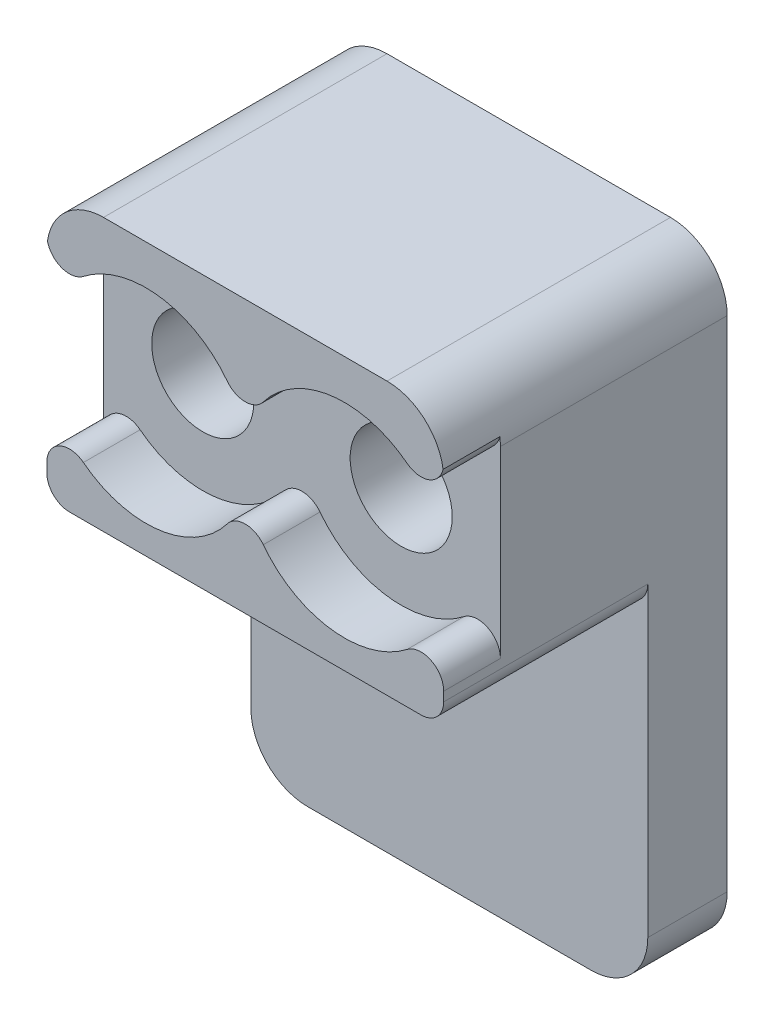
SolidWorks part; units mm, degrees
other "Markup1"
sketch "Sketch4" plane through (17.78, 27.432, 12.7) normal (0.9333, 0.0177, 0.3587) x (0.3579, 0.0365, -0.933)
ref_plane "Front Plane" through (0, 0, 0) normal (0, 0, 1) x (1, 0, 0)
ref_plane "Top Plane" through (0, 0, 0) normal (0, 1, 0) x (1, 0, 0)
ref_plane "Right Plane" through (0, 0, 0) normal (1, 0, 0) x (0, 0, -1)
sketch "Sketch1" plane through (0, 0, 0) normal (1, 0, 0) x (0, 0, -1)
  line L0 (0, 0) -> (0, 27.432)
  line L1 (0, 27.432) -> (-12.7, 27.432)
  line L2 (-12.7, 27.432) -> (-12.7, 15.24)
  line L3 (-12.7, 15.24) -> (-3.556, 15.24)
  line L4 (-3.556, 15.24) -> (-3.556, 0)
  line L5 (-3.556, 0) -> (0, 0)
  point P3 (-1.778, 0)
  dimension "D1" = 3.556
  dimension "D2" = 15.24
  dimension "D3" = 12.192
  dimension "D4" = 12.7
extrude "Boss-Extrude1" add sketch "Sketch1" along normal blind 17.78 contours L5 L0 L1 L2 L3 L4
sketch "Sketch2" plane through (0, 0, 12.7) normal (0, 0, 1) x (1, 0, 0)
  line L0 (8.89, 27.432) -> (8.89, 15.24) construction
  line L1 (17.78, 27.432) -> (0, 27.432) construction
  line L2 (17.78, 15.24) -> (0, 15.24) construction
  circle A0 centre (4.445, 21.082) radius 2.286
  circle A1 centre (13.335, 21.082) radius 2.286
  dimension "D2" = 4.572
  dimension "D1" = 4.445
  dimension "D3" = 6.35
extrude "Cut-Extrude1" cut sketch "Sketch2" against normal through all
sketch "Sketch3" plane through (0, 0, 12.7) normal (0, 0, 1) x (1, 0, 0)
  circle A0 centre (4.445, 21.082) radius 4.572
  circle A1 centre (13.335, 21.082) radius 4.572
  circle M2 centre (4.445, 21.082) radius 2.286
  circle M3 centre (13.335, 21.082) radius 2.286
  line M4 (0, 27.432) -> (0, 15.24)
  line M6 (17.78, 15.24) -> (17.78, 27.432)
  dimension "D1" = 9.144
extrude "Cut-Extrude2" cut sketch "Sketch3" against normal blind 2.54 contours A1 A0 M4 M2 | A1 A0 M6 M3 | A0 A1
fillet "Fillet1" radius 1.016 8 edges at (0, 20.0119, 11.43) (0, 22.1521, 11.43) (17.78, 22.1521, 11.43) (17.78, 20.0119, 11.43) (17.78, 15.24, 8.128) (0, 15.24, 8.128) (8.89, 22.1521, 11.43) (8.89, 20.0119, 11.43)
fillet "Fillet2" radius 2.54 4 edges at (0, 27.432, 6.35) (17.78, 27.432, 6.35) (0, 0, 1.778) (17.78, 0, 1.778)
